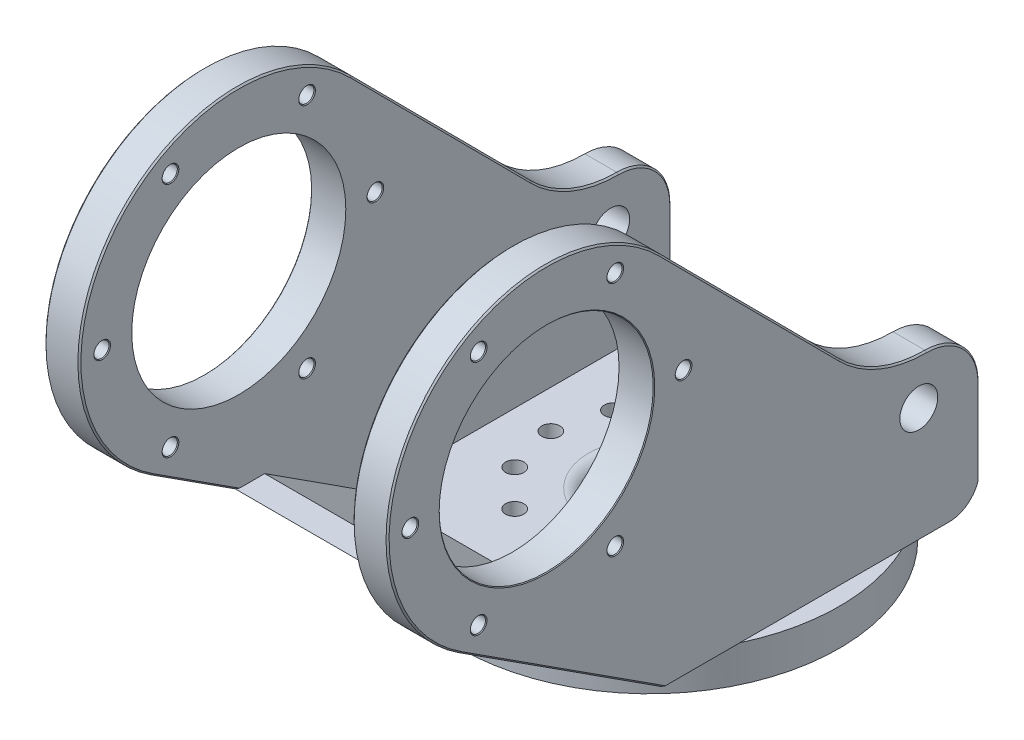
SolidWorks part; units mm, degrees
ref_plane "前视基准面" through (0, 0, 0) normal (0, 0, 1) x (1, 0, 0)
ref_plane "上视基准面" through (0, 0, 0) normal (0, 1, 0) x (1, 0, 0)
ref_plane "右视基准面" through (0, 0, 0) normal (1, 0, 0) x (0, 0, -1)
other "Configuration Table"
sketch "草图1" plane through (0, 0, 0) normal (0, 1, 0) x (1, 0, 0)
  circle A0 centre (0, 0) radius 125
  dimension "D1" = 250
extrude "凸台-拉伸1" add sketch "草图1" along normal mid plane 29
sketch "草图2" plane through (0, 0, 0) normal (1, 0, 0) x (0, 0, -1)
  line L0 (0, -14.5) -> (55, -14.5)
  line L1 (-125, -14.5) -> (125, -14.5) construction
  line L2 (55, -14.5) -> (55, -10.5)
  line L3 (55, -10.5) -> (30, -10.5)
  line L4 (30, -10.5) -> (30, 4.5)
  line L6 (125, 14.5) -> (-125, 14.5) construction
  line L7 (0, -14.5) -> (0, 14.5)
  line L8 (0, 14.5) -> (40, 14.5)
  arc A0 (30, 4.5) -> (40, 14.5) centre (40, 4.5) cw
  dimension "D3" = 10
  dimension "D1" = 55
  dimension "D2" = 30
  dimension "D4" = 4
revolve "切除-旋转1" cut sketch "草图2" angle 360 about L7
sketch "草图3" plane through (0, 14.5, 0) normal (0, 1, 0) x (1, 0, 0)
  circle A0 centre (0, 0) radius 65 construction
  circle A1 centre (0, 65) radius 6
  circle A2 centre (32.5, 56.2917) radius 6
  circle A3 centre (56.2917, 32.5) radius 6
  circle A4 centre (65, 0) radius 6
  circle A5 centre (56.2917, -32.5) radius 6
  circle A6 centre (32.5, -56.2917) radius 6
  circle A7 centre (0, -65) radius 6
  circle A8 centre (-32.5, -56.2917) radius 6
  circle A9 centre (-56.2917, -32.5) radius 6
  circle A10 centre (-65, 0) radius 6
  circle A11 centre (-56.2917, 32.5) radius 6
  circle A12 centre (-32.5, 56.2917) radius 6
  point P6 (0, 0)
  point P7 (56.2917, 32.5)
  point P29 (0, 0)
  dimension "D1" = 130
  dimension "D2" = 12
  dimension "D3" = 12
extrude "切除-拉伸1" cut sketch "草图3" against normal blind 29
sketch "草图4" plane through (0, 14.5, 0) normal (0, 1, 0) x (1, 0, 0)
  line L1 (-90, 125) -> (90, 125)
  line L2 (-90, 125) -> (-90, -125)
  line L3 (-90, -125) -> (90, -125)
  line L4 (90, 125) -> (90, -125)
  line L5 (-90, 125) -> (90, -125) construction
  line L6 (-90, -125) -> (90, 125) construction
  circle A0 centre (0, 0) radius 125 construction
  point P0 (0, 0)
  dimension "D1" = 180
extrude "切除-拉伸2" cut sketch "草图4" against normal blind 5 flip side to cut
sketch "草图5" plane through (-90, 0, 0) normal (-1, 0, 0) x (0, 0, 1)
  line L0 (-104.4, 9.5) -> (104.4, 9.5)
  line L1 (104.4, 9.5) -> (237.47, 95.3235)
  line L2 (106.086, 257.581) -> (-12.658, 138.1055)
  line L3 (-104.4, 79.5) -> (-104.4, 9.5)
  arc A0 (237.47, 95.3235) -> (106.086, 257.581) centre (180.5598, 183.5632) ccw
  arc A1 (-12.658, 138.1055) -> (-69.4, 114.5) centre (-69.4, 194.5) cw
  arc A2 (-69.4, 114.5) -> (-104.4, 79.5) centre (-69.4, 79.5) ccw
  circle A3 centre (180.5598, 183.5632) radius 90 construction
  circle A4 centre (270.5598, 183.5632) radius 5
  circle A5 centre (225.5598, 105.6209) radius 5
  circle A6 centre (135.5598, 105.6209) radius 5
  circle A7 centre (90.5598, 183.5632) radius 5
  circle A8 centre (135.5598, 261.5054) radius 5
  circle A9 centre (225.5598, 261.5054) radius 5
  circle A10 centre (180.5598, 183.5632) radius 70.5
  circle A11 centre (-64.4, 84.5) radius 12.5
  point P15 (0, 9.5)
  point P31 (180.5598, 183.5632)
  dimension "D4" = 105
  dimension "D5" = 80
  dimension "D6" = 35
  dimension "D9" = 180
  dimension "D10" = 10
  dimension "D12" = 141
  dimension "D15" = 25
  dimension "D1" = 208.8
  dimension "D2" = 32.82
  dimension "D3" = 133.07
  dimension "D7" = 185
  dimension "D8" = 105
  dimension "D13" = 40
  dimension "D14" = 30
  dimension "D11" = 6
extrude "凸台-拉伸2" add sketch "草图5" along normal blind 23
mirror "镜向1" about plane through (0, 0, 0) normal (1, 0, 0) of "凸台-拉伸2"
chamfer "倒角1" distance 1 angle 45 25 edges at (0, -10.5, -30) (90, 52.4118, 170.935) (90, 249.6389, 262.1625) (90, 44.5, -104.4) (90, 197.8432, 46.714) (90, 104.2487, -94.1487) (90, 120.6367, -38.6719) (113, 52.4118, 170.935) (113, 249.6389, 262.1625) (113, 44.5, -104.4) (113, 197.8432, 46.714) (113, 104.2487, -94.1487) (113, 120.6367, -38.6719) (-113, 52.4118, 170.935) (-113, 249.6389, 262.1625) (-113, 197.8432, 46.714) (-113, 120.6367, -38.6719) (-113, 104.2487, -94.1487) (-113, 44.5, -104.4) (-90, 52.4118, 170.935) (-90, 249.6389, 262.1625) (-90, 44.5, -104.4) (-90, 197.8432, 46.714) (-90, 104.2487, -94.1487) (-90, 120.6367, -38.6719)
chamfer "倒角2" distance 0.5 angle 45 26 edges at (-90, 105.6209, 230.5598) (-113, 105.6209, 230.5598) (-90, 105.6209, 140.5598) (-113, 105.6209, 140.5598) (-90, 183.5632, 95.5598) (-113, 183.5632, 95.5598) (-90, 261.5054, 140.5598) (-113, 261.5054, 140.5598) (-90, 261.5054, 230.5598) (-113, 261.5054, 230.5598) (-90, 183.5632, 275.5598) (-113, 183.5632, 275.5598) (90, 183.5632, 95.5598) (113, 183.5632, 95.5598) (90, 261.5054, 140.5598) (113, 261.5054, 140.5598) (90, 261.5054, 230.5598) (113, 261.5054, 230.5598) (90, 183.5632, 275.5598) (113, 183.5632, 275.5598) (90, 105.6209, 140.5598) (113, 105.6209, 140.5598) (90, 105.6209, 230.5598) (113, 105.6209, 230.5598) (-113, 183.5632, 251.0598) (113, 183.5632, 251.0598)
fillet "圆角1" radius 20 2 edges at (101.5, 9.5, -104.4) (-101.5, 9.5, -104.4)
sketch "草图6" plane through (-113, 0, 0) normal (-1, 0, 0) x (0, 0, 1)
  line L0 (237.47, 95.3235) -> (104.4, 9.5) construction
  line L1 (181.9254, 59.5) -> (112.1525, 14.5)
  line L2 (163.4752, 59.5) -> (93.7024, 14.5)
  line L3 (232.05, 103.7273) -> (98.98, 17.9038) construction
  line L4 (125, 14.5) -> (86.7468, 14.5) construction
  line L5 (237.47, 95.3235) -> (104.4, 9.5) construction
  line L6 (93.7024, 14.5) -> (112.1525, 14.5)
  line L7 (163.4752, 59.5) -> (181.9254, 59.5)
  dimension "D2" = 45
  dimension "D1" = 10
extrude "凸台-拉伸3" add sketch "草图6" against normal up to surface (203 mm away) up to face at (90, 183.5632, 85.0598)
